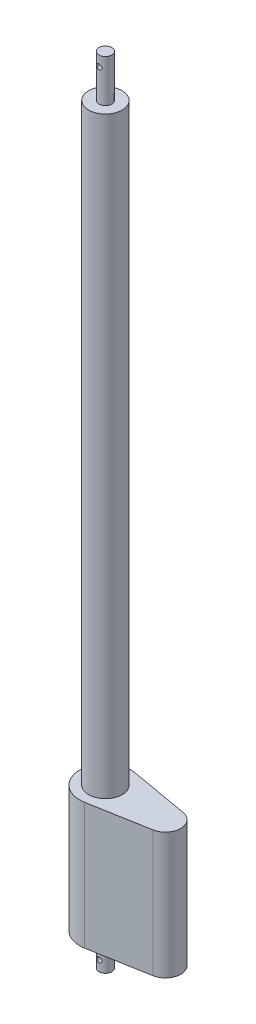
SolidWorks part; units mm, degrees
ref_plane "Front" through (0, 0, 0) normal (0, 0, 1) x (1, 0, 0)
ref_plane "Top" through (0, 0, 0) normal (0, 1, 0) x (1, 0, 0)
ref_plane "Right" through (0, 0, 0) normal (1, 0, 0) x (0, 0, -1)
sketch "Sketch7" plane through (0, 0, 0) normal (1, 0, 0) x (0, 0, -1)
  line L1 (-20, 17) -> (-20, 115)
  line L4 (-13, 575) -> (-5, 575)
  line L5 (-5, 575) -> (-5, 608)
  line L6 (-5, 608) -> (0, 608)
  line L7 (0, 608) -> (0, -8)
  line L9 (-5, -8) -> (0, -8)
  line L10 (-13, 575) -> (-13, 115)
  line L11 (-13, 115) -> (-20, 115)
  line L12 (-5, -8) -> (-5, 17)
  line L13 (-5, 17) -> (-20, 17)
  point P11 (0, 0)
  point P12 (0, 600)
  point P13 (0, 600)
  dimension "D1" = 8
  dimension "D2" = 8
  dimension "D3" = 98
  dimension "D5" = 25
  dimension "D6" = 0
  dimension "D4" = 600
  dimension "D7" = 13
  dimension "D8" = 20
  dimension "D11" = 5
  dimension "D9" = 25
  dimension "D10" = 5
revolve "Revolve2" add sketch "Sketch7" angle 360 about L7
sketch "Sketch8" plane through (0, 0, 0) normal (0, 0, 1) x (1, 0, 0)
  line L0 (-5, -8) -> (5, -8) construction
  line L2 (0, 608) -> (0, 600) construction
  line L3 (5, 608) -> (-5, 608) construction
  line L4 (-5, -8) -> (5, -8) construction
  line L5 (0, -8) -> (0, 0) construction
  circle A1 centre (0, 600) radius 2
  circle A2 centre (0, 0) radius 2
  dimension "D2" = 8
  dimension "D1" = 4
  dimension "D4" = 4
  dimension "D3" = 8
extrude "Cut-Extrude2" cut sketch "Sketch8" against normal through all and the other way through all
sketch "Sketch10" plane through (0, 115, 0) normal (0, 1, 0) x (1, 0, 0)
  line L0 (0, 0) -> (46.5567, 0) construction
  line L1 (3.491, 19.693) -> (48.6292, 11.6912)
  line L2 (48.6292, -11.6912) -> (3.491, -19.693)
  circle A1 centre (0, 0) radius 20 construction
  arc A2 (48.6292, 11.6912) -> (48.6292, -11.6912) centre (46.5567, 0) cw
  arc A3 (3.491, 19.693) -> (3.491, -19.693) centre (0, 0) ccw
extrude "Boss-Extrude4" add sketch "Sketch10" against normal up to surface (98 mm away) up to face at (0, 17, 5)
sketch "Sketch11" plane through (0, 0, 0) normal (0, 0, 1) x (1, 0, 0)
  line L0 (0, 600) -> (0, 0)
equation "\"mountingHoleDistance\"=8"
equation "\"actuatorLength\"= 0"
equation "\"D1@Sketch7\"=\"mountingHoleDistance\""
equation "\"D2@Sketch7\"=\"mountingHoleDistance\""
equation "\"MotorHousingHeight\"= 98"
equation "\"D3@Sketch7\"=\"MotorHousingHeight\""
equation "\"D6@Sketch7\"=\"actuatorLength\""
equation "\"acutatorMinimumLength\"=600"
equation "\"D4@Sketch7\"=\"acutatorMinimumLength\""
equation "\"D3@Sketch8\"=\"mountingHoleDistance\""
equation "\"D2@Sketch8\"=\"mountingHoleDistance\""
